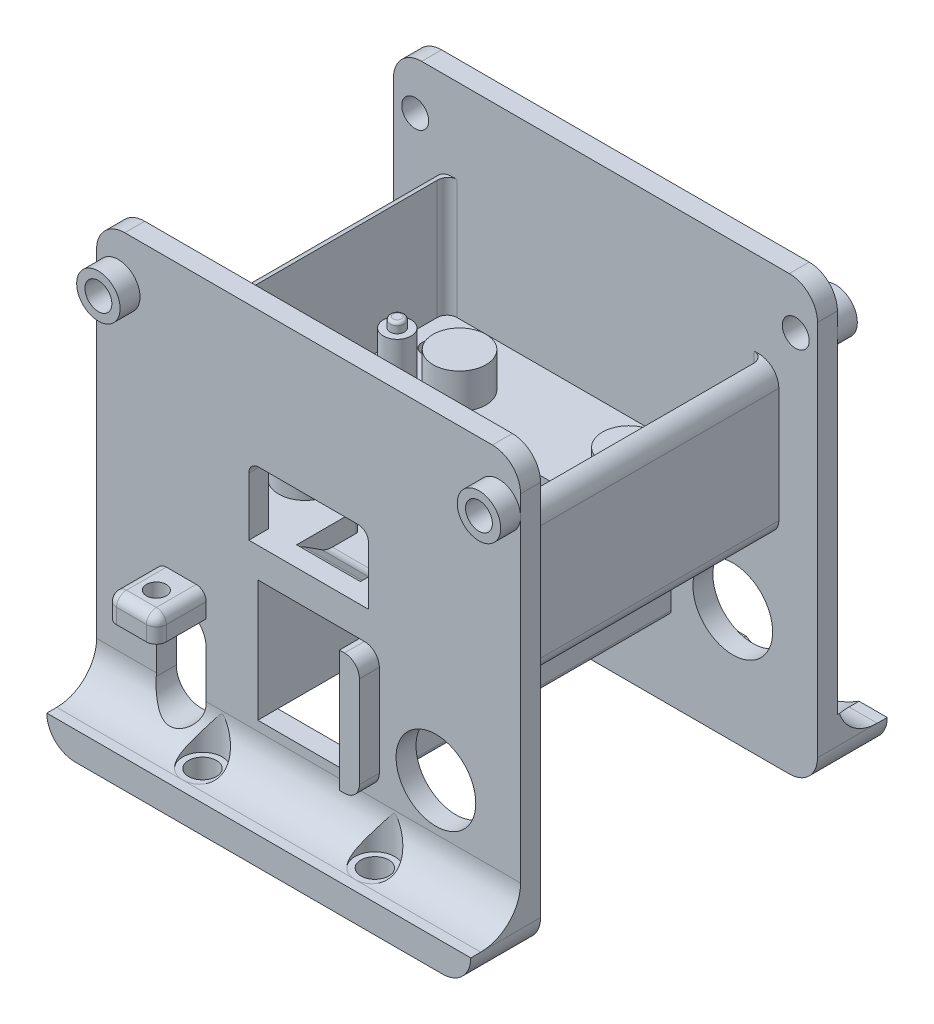
SolidWorks part; units mm, degrees
other "标注1"
sketch "草图55" plane through (-21.28, -20, 20.9) normal (0, 0, 1) x (1, 0, 0)
material "尼龙 101"
ref_plane "前视基准面" through (0, 0, 0) normal (0, 0, 1) x (1, 0, 0)
ref_plane "上视基准面" through (0, 0, 0) normal (0, 1, 0) x (1, 0, 0)
ref_plane "右视基准面" through (0, 0, 0) normal (1, 0, 0) x (0, 0, -1)
other "Configuration Table"
sketch "草图1" plane through (0, 0, 0) normal (0, 1, 0) x (1, 0, 0)
  line L1 (-15.9, 13.9) -> (15.9, 13.9)
  line L2 (-15.9, 13.9) -> (-15.9, -13.9)
  line L3 (-15.9, -13.9) -> (15.9, -13.9)
  line L4 (15.9, 13.9) -> (15.9, -13.9)
  line L5 (-15.9, 13.9) -> (15.9, -13.9) construction
  line L6 (-15.9, -13.9) -> (15.9, 13.9) construction
  point P0 (0, 0)
  dimension "D1" = 31.8
  dimension "D2" = 27.8
extrude "凸台-拉伸1" add sketch "草图1" along normal blind 3
sketch "草图2" plane through (0, 3, 0) normal (0, 1, 0) x (1, 0, 0)
  line L0 (0, 0) -> (0, 5.35) construction
  line L1 (-5.35, 5.35) -> (5.35, 5.35)
  line L2 (5.35, 5.35) -> (5.35, -7.55)
  line L3 (5.35, -7.55) -> (4.35, -7.55)
  line L4 (4.35, -7.55) -> (4.35, 4.35)
  line L5 (4.35, 4.35) -> (-4.35, 4.35)
  line L6 (-4.35, -7.55) -> (-4.35, 4.35)
  line L7 (-5.35, -7.55) -> (-4.35, -7.55)
  line L8 (-5.35, 5.35) -> (-5.35, -7.55)
  point P9 (0, 4.35)
  dimension "D1" = 8.7
  dimension "D2" = 11.9
  dimension "D3" = 4.35
  dimension "D4" = 1
  dimension "D5" = 1
extrude "凸台-拉伸2" add sketch "草图2" along normal blind 1.5
sketch "草图5" plane through (0, 3, 0) normal (0, 1, 0) x (1, 0, 0)
  line L0 (0, 13.9) -> (0, 0) construction
  line L1 (15.9, 13.9) -> (-15.9, 13.9) construction
  line L2 (0, 0) -> (15.9, 0) construction
  line L3 (15.9, -13.9) -> (15.9, 13.9) construction
  circle A0 centre (12.5, 5.5) radius 1.4
  circle A1 centre (12.5, -5.5) radius 1.4
  circle A2 centre (-12.5, -5.5) radius 1.4
  circle A3 centre (-12.5, 5.5) radius 1.4
  dimension "D1" = 2.8
  dimension "D2" = 25
  dimension "D3" = 11
extrude "凸台-拉伸3" add sketch "草图5" along normal blind 4.5
sketch "草图6" plane through (0, 7.5, 0) normal (0, 1, 0) x (1, 0, 0)
  circle A0 centre (-12.5, -5.5) radius 0.725
  circle A1 centre (-12.5, 5.5) radius 0.725
  circle A2 centre (12.5, 5.5) radius 0.725
  circle A3 centre (12.5, -5.5) radius 0.725
  dimension "D1" = 1.45
extrude "凸台-拉伸4" add sketch "草图6" along normal blind 1
sketch "草图7" plane through (0, 3, 0) normal (0, 1, 0) x (1, 0, 0)
  line L0 (0, 0) -> (0, 13.9) construction
  line L1 (15.9, 13.9) -> (-15.9, 13.9) construction
  line L2 (0, 0) -> (15.9, 0) construction
  line L3 (15.9, -13.9) -> (15.9, 13.9) construction
  circle A0 centre (13.5, 10) radius 1
  circle A1 centre (-13.5, 10) radius 1
  circle A2 centre (-13.5, -10) radius 1
  circle A3 centre (13.5, -10) radius 1
  dimension "D1" = 2
  dimension "D2" = 20
  dimension "D3" = 27
extrude "切除-拉伸1" cut sketch "草图7" against normal blind 10
sketch "草图8" plane through (0, 0, 0) normal (0, -1, 0) x (1, 0, 0)
  circle A0 centre (-13.5, 10) radius 2
  circle A1 centre (13.5, 10) radius 2
  circle A2 centre (13.5, -10) radius 2
  circle A3 centre (-13.5, -10) radius 2
  dimension "D1" = 4
extrude "切除-拉伸2" cut sketch "草图8" against normal blind 1
fillet "圆角1" radius 1 4 edges at (-15.9, 1.5, -13.9) (15.9, 1.5, -13.9) (-15.9, 1.5, 13.9) (15.9, 1.5, 13.9)
sketch "草图9" plane through (0, 3, 0) normal (0, 1, 0) x (1, 0, 0)
  line L0 (0, 13.9) -> (0, 0) construction
  line L1 (14.9, 13.9) -> (-14.9, 13.9) construction
  line L2 (0, 0) -> (15.9, 0) construction
  line L3 (15.9, -12.9) -> (15.9, 12.9) construction
  circle A0 centre (8.5, 7.75) radius 2.65
  circle A1 centre (-8.5, 7.75) radius 2.65
  circle A2 centre (-8.5, -7.75) radius 2.65
  circle A3 centre (8.5, -7.75) radius 2.65
  dimension "D1" = 17
  dimension "D2" = 15.5
  dimension "D3" = 5.3
extrude "凸台-拉伸5" add sketch "草图9" along normal blind 3.5
fillet "圆角2" radius 0.3 4 edges at (12.5, 8.5, -4.775) (12.5, 8.5, 6.225) (-12.5, 8.5, 6.225) (-12.5, 8.5, -4.775)
sketch "草图15" plane through (0, 3, 0) normal (0, 1, 0) x (1, 0, 0)
  line L0 (0, 0) -> (0, 13.9) construction
  line L1 (14.9, 13.9) -> (-14.9, 13.9) construction
  line L2 (-4.35, 4.35) -> (4.35, 4.35)
  line L3 (4.35, 4.35) -> (4.35, -7.55)
  line L4 (4.35, -7.55) -> (3.2, -7.55)
  line L5 (3.2, -7.55) -> (3.2, -13.9)
  line L6 (-14.9, -13.9) -> (14.9, -13.9) construction
  line L7 (3.2, -13.9) -> (-3.2, -13.9)
  line L8 (-3.2, -7.55) -> (-3.2, -13.9)
  line L9 (-4.35, -7.55) -> (-3.2, -7.55)
  line L10 (-4.35, 4.35) -> (-4.35, -7.55)
  line L11 (4.35, 4.35) -> (4.35, -7.55) construction
  point P14 (0, -13.9)
  point P17 (0, 4.35)
  dimension "D1" = 6.4
extrude "切除-拉伸8" cut sketch "草图15" against normal blind 2
sketch "草图17" plane through (0, 4.5, 0) normal (0, 1, 0) x (1, 0, 0)
  line L8 (-4.35, -7.55) -> (-4.35, 4.35)
  line L9 (-4.35, 4.35) -> (4.35, 4.35)
  line L10 (4.35, 4.35) -> (4.35, -7.55)
  line L11 (4.35, -7.55) -> (5.35, -7.55)
  line L12 (5.35, -7.55) -> (5.35, 5.35)
  line L13 (5.35, 5.35) -> (-5.35, 5.35)
  line L14 (-5.35, 5.35) -> (-5.35, -7.55)
  line L15 (-5.35, -7.55) -> (-4.35, -7.55)
  line L16 (-4.35, -7.55) -> (-4.35, 4.35)
  line L17 (-4.35, 4.35) -> (4.35, 4.35)
  line L18 (4.35, 4.35) -> (4.35, -7.55)
  line L19 (4.35, -7.55) -> (5.35, -7.55)
  line L20 (5.35, -7.55) -> (5.35, 5.35)
  line L21 (5.35, 5.35) -> (-5.35, 5.35)
  line L22 (-5.35, 5.35) -> (-5.35, -7.55)
  line L23 (-5.35, -7.55) -> (-4.35, -7.55)
  dimension "D1" = 0
extrude "切除-拉伸9" cut sketch "草图17" against normal blind 1.5
sketch "草图18" plane through (3.2, 0, 0) normal (-1, 0, 0) x (0, 0, 1)
  line L0 (13.9, 1) -> (10.9, 1)
  line L2 (13.9, 1) -> (13.9, 3) construction
  line L3 (13.9, 2.6) -> (13.9, 1)
  line L5 (13.9, 3) -> (13.9, 0) construction
  line L6 (13.9, 2.6) -> (13.4, 2.6)
  line L7 (13.4, 2.6) -> (10.9, 1)
  line L8 (13.9, 3) -> (12.9, 3) construction
  dimension "D1" = 3
  dimension "D2" = 0.4
  dimension "D3" = 0.5
extrude "凸台-拉伸6" add sketch "草图18" along normal up to surface (6.4 mm away) up to face at (-3.2, 2, 10.725)
fillet "圆角3" radius 2 1 edges at (0, 1, 10.9)
fillet "圆角5" radius 1 1 edges at (0, 2.6, 13.4)
fillet "圆角6" radius 0.4 2 edges at (3.2, 2, 7.55) (-3.2, 2, 7.55)
sketch "草图21" plane through (0, 0, 0) normal (0, -1, 0) x (1, 0, 0)
  line L0 (-14.9, 13.9) -> (14.9, 13.9) construction
  line L1 (-15.9, -12.9) -> (-15.9, 12.9) construction
  line L2 (14.9, -13.9) -> (-14.9, -13.9) construction
  line L3 (15.9, 12.9) -> (15.9, -12.9) construction
  line L4 (-14.9, 13.9) -> (14.9, 13.9)
  line L5 (-15.9, -12.9) -> (-15.9, 12.9)
  line L6 (14.9, -13.9) -> (-14.9, -13.9)
  line L7 (15.9, 12.9) -> (15.9, -12.9)
  line L9 (-17.4, 15.9) -> (17.4, 15.9)
  line L10 (-17.4, 15.9) -> (-17.4, -15.9)
  line L11 (-17.4, -15.9) -> (17.4, -15.9)
  line L12 (17.4, 15.9) -> (17.4, -15.9)
  arc A0 (15.9, 12.9) -> (14.9, 13.9) centre (14.9, 12.9) ccw construction
  arc A1 (-14.9, 13.9) -> (-15.9, 12.9) centre (-14.9, 12.9) ccw construction
  arc A2 (-15.9, -12.9) -> (-14.9, -13.9) centre (-14.9, -12.9) ccw construction
  arc A3 (14.9, -13.9) -> (15.9, -12.9) centre (14.9, -12.9) ccw construction
  arc A4 (15.9, 12.9) -> (14.9, 13.9) centre (14.9, 12.9) ccw
  arc A5 (-14.9, 13.9) -> (-15.9, 12.9) centre (-14.9, 12.9) ccw
  arc A6 (-15.9, -12.9) -> (-14.9, -13.9) centre (-14.9, -12.9) ccw
  arc A7 (14.9, -13.9) -> (15.9, -12.9) centre (14.9, -12.9) ccw
  dimension "D1" = 1.5
  dimension "D2" = 1.5
  dimension "D3" = 2
  dimension "D4" = 2
extrude "凸台-拉伸7" add sketch "草图21" against normal blind 15
sketch "草图22" plane through (0, 0, 15.9) normal (0, 0, 1) x (1, 0, 0)
  line L2 (-21.28, 0) -> (-21.28, 20.67)
  line L3 (-18.45, 23.5) -> (18.45, 23.5)
  line L4 (21.28, 0) -> (21.28, 20.67)
  line L5 (-21.28, 0) -> (21.28, 23.5) construction
  line L6 (-21.28, 23.5) -> (21.28, 0) construction
  line L7 (0, 0) -> (0, 23.5) construction
  line L10 (-21.28, 0) -> (-21.28, -17.17)
  line L11 (-18.45, -20) -> (18.45, -20)
  line L12 (21.28, 0) -> (21.28, -17.17)
  arc A0 (-21.28, 20.67) -> (-18.45, 23.5) centre (-18.45, 20.67) cw
  arc A1 (18.45, 23.5) -> (21.28, 20.67) centre (18.45, 20.67) cw
  arc A4 (18.45, -20) -> (21.28, -17.17) centre (18.45, -17.17) ccw
  arc A5 (-21.28, -17.17) -> (-18.45, -20) centre (-18.45, -17.17) ccw
  circle A9 centre (19.1, 18.67) radius 1.35
  circle A10 centre (-19.1, 18.67) radius 1.35
  point P4 (0, 11.75)
  point P22 (21.28, -20)
  dimension "D3" = 2.83
  dimension "D4" = 2.83
  dimension "D8" = 2.83
  dimension "D1" = 42.56
  dimension "D2" = 23.5
  dimension "D7" = 20
extrude "凸台-拉伸8" add sketch "草图22" against normal blind 2
sketch "草图24" plane through (0, 0, -15.9) normal (0, 0, -1) x (-1, 0, 0)
  line L5 (-18.45, -20) -> (18.45, -20)
  line L6 (-18.45, -20) -> (18.45, -20)
  line L21 (21.28, -17.17) -> (21.28, 20.67)
  line L22 (18.45, 23.5) -> (-18.45, 23.5)
  line L23 (-21.28, 20.67) -> (-21.28, -17.17)
  line L37 (21.28, -17.17) -> (21.28, 20.67)
  line L38 (18.45, 23.5) -> (-18.45, 23.5)
  line L39 (-21.28, 20.67) -> (-21.28, -17.17)
  arc A2 (21.28, 20.67) -> (18.45, 23.5) centre (18.45, 20.67) ccw
  arc A3 (-18.45, 23.5) -> (-21.28, 20.67) centre (-18.45, 20.67) ccw
  arc A4 (21.28, 20.67) -> (18.45, 23.5) centre (18.45, 20.67) ccw
  arc A5 (-18.45, 23.5) -> (-21.28, 20.67) centre (-18.45, 20.67) ccw
  circle A10 centre (19.1, 18.67) radius 1.35 construction
  circle A11 centre (-19.1, 18.67) radius 1.35 construction
  arc A12 (-21.28, -17.17) -> (-18.45, -20) centre (-18.45, -17.17) ccw
  arc A13 (-21.28, -17.17) -> (-18.45, -20) centre (-18.45, -17.17) ccw
  arc A14 (18.45, -20) -> (21.28, -17.17) centre (18.45, -17.17) ccw
  arc A15 (18.45, -20) -> (21.28, -17.17) centre (18.45, -17.17) ccw
  circle A16 centre (19.1, 18.67) radius 1.35
  circle A17 centre (-19.1, 18.67) radius 1.35
  dimension "D1" = 0
extrude "凸台-拉伸9" add sketch "草图24" against normal blind 2
sketch "草图25" plane through (0, 0, 15.9) normal (0, 0, 1) x (1, 0, 0)
  line L1 (-5, 9.85) -> (5, 9.85)
  line L2 (-6, 8.85) -> (-6, 3)
  line L4 (6, 8.85) -> (6, 3)
  line L5 (-6, 3) -> (6, 3)
  line L9 (-6, 3) -> (6, 9.85) construction
  arc A0 (5, 9.85) -> (6, 8.85) centre (5, 8.85) cw
  arc A1 (-5, 9.85) -> (-6, 8.85) centre (-5, 8.85) ccw
  point P5 (6, 9.85)
  point P8 (0, 6.425)
  point P9 (-6, 9.85)
  dimension "D2" = 1
  dimension "D1" = 12
extrude "切除-拉伸10" cut sketch "草图25" against normal blind 2
sketch "草图27" plane through (0, 0, 15.9) normal (0, 0, 1) x (1, 0, 0)
  line L0 (-5.1, 0) -> (5.1, -12.2) construction
  line L5 (-5.1, 0) -> (5.1, 0) construction
  line L16 (-17.4, 0) -> (17.4, 0) construction
  line L18 (-5.1, 0) -> (-5.1, -12.2)
  line L20 (5.1, 0) -> (5.1, -12.2)
  line L21 (-6.6, 0) -> (-6.6, -11.7)
  line L26 (6.6, 0) -> (6.6, -11.7)
  line L31 (-6.6, 0) -> (-5.1, 0)
  line L33 (-6.1, -12.2) -> (-5.1, -12.2)
  line L34 (-6.6, 1.5) -> (6.6, 1.5) construction
  line L35 (0, 0) -> (0, -4.0507) construction
  line L36 (6.6, 1.5) -> (6.6, -13.7) construction
  line L37 (-6.6, 1.5) -> (-6.6, -13.7) construction
  line L38 (5.1, 0) -> (6.6, 0)
  line L39 (-6.6, -13.7) -> (6.6, -13.7) construction
  line L40 (-5.1, -12.2) -> (5.1, -12.2) construction
  line L41 (5.1, -12.2) -> (6.1, -12.2)
  arc A4 (6.1, -12.2) -> (6.6, -11.7) centre (6.1, -11.7) ccw
  arc A5 (-6.6, -11.7) -> (-6.1, -12.2) centre (-6.1, -11.7) ccw
  point P6 (-2.5, 0)
  point P7 (6.9808, -17.5163)
  point P19 (6.6, -12.2)
  point P24 (0, -6.1)
  dimension "D4" = 0.5
  dimension "D1" = 10.2
  dimension "D2" = 12.2
  dimension "D3" = 1.5
extrude "凸台-拉伸10" add sketch "草图27" against normal up to surface (29.8 mm away) up to face at (0, 8.25, -13.9)
sketch "草图35" plane through (0, 0, 15.9) normal (0, 0, 1) x (1, 0, 0)
  line L1 (-5.1, 0) -> (5.1, 0)
  line L2 (-5.1, 0) -> (-5.1, -12.2)
  line L3 (-5.1, -12.2) -> (5.1, -12.2)
  line L4 (5.1, 0) -> (5.1, -12.2)
extrude "切除-拉伸14" cut sketch "草图35" against normal through all
sketch "草图43" plane through (0, 0, 15.9) normal (0, 0, 1) x (1, 0, 0)
  line L0 (-21.28, -17.17) -> (21.28, -17.17)
  line L1 (-18.45, -20) -> (18.45, -20) construction
  line L2 (-18.45, -20) -> (18.45, -20)
  arc A1 (18.45, -20) -> (21.28, -17.17) centre (18.45, -17.17) ccw construction
  arc A3 (-21.28, -17.17) -> (-18.45, -20) centre (-18.45, -17.17) ccw construction
  arc A4 (18.45, -20) -> (21.28, -17.17) centre (18.45, -17.17) ccw
  arc A5 (-21.28, -17.17) -> (-18.45, -20) centre (-18.45, -17.17) ccw
extrude "凸台-拉伸14" add sketch "草图43" along normal blind 5
sketch "草图44" plane through (-21.28, 0, 0) normal (-1, 0, 0) x (0, 0, 1)
  line L3 (15.9, -13.17) -> (15.9, -17.17)
  line L4 (15.9, -17.17) -> (19.9, -17.17)
  arc A0 (19.9, -17.17) -> (15.9, -13.17) centre (19.9, -13.17) cw
  point P8 (15.9, -17.17)
  dimension "D1" = 4
extrude "凸台-拉伸15" add sketch "草图44" against normal up to surface (42.56 mm away) up to face at (21.28, 1.75, 14.9)
sketch "草图45" plane through (0, 0, -15.9) normal (0, 0, -1) x (-1, 0, 0)
  line L0 (-18.45, -20) -> (18.45, -20) construction
  line L1 (-21.28, -17.17) -> (21.28, -17.17) construction
  line L2 (-18.45, -20) -> (18.45, -20)
  line L3 (-21.28, -17.17) -> (21.28, -17.17)
  arc A0 (-21.28, -17.17) -> (-18.45, -20) centre (-18.45, -17.17) ccw construction
  arc A1 (18.45, -20) -> (21.28, -17.17) centre (18.45, -17.17) ccw construction
  arc A2 (-21.28, -17.17) -> (-18.45, -20) centre (-18.45, -17.17) ccw
  arc A3 (18.45, -20) -> (21.28, -17.17) centre (18.45, -17.17) ccw
extrude "凸台-拉伸16" add sketch "草图45" along normal blind 5
sketch "草图46" plane through (21.28, 0, 0) normal (1, 0, 0) x (0, 0, -1)
  line L0 (15.9, -13.17) -> (15.9, -17.17)
  line L1 (15.9, -17.17) -> (19.9, -17.17)
  arc A0 (15.9, -13.17) -> (19.9, -17.17) centre (19.9, -13.17) ccw
  point P7 (15.9, -17.17)
  dimension "D1" = 4
extrude "凸台-拉伸17" add sketch "草图46" against normal up to surface (42.56 mm away) up to face at (-21.28, 1.75, -14.9)
sketch "草图36" plane through (0, 0, 15.9) normal (0, 0, 1) x (1, 0, 0)
  line L0 (-5.1, 0) -> (5.1, -12.2) construction
  line L1 (5.1, 0) -> (-5.1, -12.2) construction
  line L2 (-5.1, -12.2) -> (5.1, -12.2) construction
  line L3 (-5.1, 0) -> (-5.1, -12.2) construction
  line L6 (-5.1, -12.2) -> (-5.1, -13.2) construction
  line L7 (-5.1, -13.2) -> (22.8364, -13.2) construction
  line L8 (21.28, -13.17) -> (21.28, 20.67) construction
  line L10 (-15.28, -8.4815) -> (-15.28, -13.4815)
  line L12 (-10.28, -13.4815) -> (-10.28, -8.4815)
  circle A0 centre (0, -6.1) radius 4.5 construction
  circle A3 centre (12.78, -8.4815) radius 8.5 construction
  circle A6 centre (12.78, -8.4815) radius 5.75 construction
  circle A7 centre (12.78, -8.4815) radius 4
  arc A9 (-10.28, -8.4815) -> (-15.28, -8.4815) centre (-12.78, -8.4815) ccw
  arc A11 (-15.28, -13.4815) -> (-10.28, -13.4815) centre (-12.78, -13.4815) ccw
  point P11 (0, -6.1)
  dimension "D1" = 9
  dimension "D2" = 17
  dimension "D3" = 8
  dimension "D4" = 9
  dimension "D5" = 11.5
extrude "切除-拉伸15" cut sketch "草图36" against normal through all both and the other way through all
sketch "草图37" plane through (0, 0, 15.9) normal (0, 0, 1) x (1, 0, 0)
  line L0 (-15.28, -5.9815) -> (-15.28, -3.4815)
  line L1 (-15.28, -3.4815) -> (-10.28, -3.4815)
  line L2 (-10.28, -3.4815) -> (-10.28, -5.9815)
  line L3 (-15.28, -5.9815) -> (-10.28, -5.9815)
extrude "凸台-拉伸11" add sketch "草图37" along normal blind 5
sketch "草图38" plane through (0, 0, -15.9) normal (0, 0, -1) x (-1, 0, 0)
  line L0 (15.28, -3.4815) -> (15.28, -5.9815) construction
  line L1 (10.28, -5.9815) -> (10.28, -3.4815) construction
  line L2 (10.28, -3.4815) -> (15.28, -3.4815) construction
  line L3 (15.28, -3.4815) -> (15.28, -5.9815)
  line L4 (10.28, -5.9815) -> (10.28, -3.4815)
  line L5 (10.28, -3.4815) -> (15.28, -3.4815)
  line L6 (10.28, -5.9815) -> (15.28, -5.9815)
extrude "凸台-拉伸12" add sketch "草图38" along normal blind 5
fillet "圆角7" radius 1 2 edges at (-10.28, -4.7315, 20.9) (-15.28, -4.7315, 20.9)
fillet "圆角8" radius 1 2 edges at (-10.28, -4.7315, -20.9) (-15.28, -4.7315, -20.9)
sketch "草图41" plane through (0, 0, 15.9) normal (0, 0, 1) x (1, 0, 0)
  line L1 (5.1, 0) -> (5.6, 0)
  line L2 (5.1, 0) -> (5.1, -12.2)
  line L3 (5.1, -12.2) -> (5.6, -12.2)
  line L4 (7.1, -1.5) -> (7.1, -10.7)
  arc A0 (5.6, -12.2) -> (7.1, -10.7) centre (5.6, -10.7) ccw
  arc A1 (7.1, -1.5) -> (5.6, 0) centre (5.6, -1.5) ccw
  dimension "D1" = 1.5
  dimension "D2" = 2
extrude "凸台-拉伸13" add sketch "草图41" along normal blind 2
sketch "草图42" plane through (0, -3.4815, 0) normal (0, 1, 0) x (1, 0, 0)
  line L0 (-14.9871, 20.6071) -> (-10.28, 15.9) construction
  line L1 (-15.28, -15.9) -> (-10.5729, -20.6071) construction
  line L2 (-10.5729, 20.6071) -> (-15.28, 15.9) construction
  line L3 (-10.28, -15.9) -> (-14.9871, -20.6071) construction
  arc A0 (-14.28, 20.9) -> (-15.28, 19.9) centre (-14.28, 19.9) ccw construction
  arc A1 (-10.28, 19.9) -> (-11.28, 20.9) centre (-11.28, 19.9) ccw construction
  arc A2 (-11.28, -20.9) -> (-10.28, -19.9) centre (-11.28, -19.9) ccw construction
  arc A3 (-15.28, -19.9) -> (-14.28, -20.9) centre (-14.28, -19.9) ccw construction
  circle A4 centre (-12.78, -18.4) radius 1
  circle A5 centre (-12.78, 18.4) radius 1
  point P24 (-12.78, 18.4)
  point P25 (-12.78, -18.4)
  dimension "D1" = 2
  dimension "D2" = 2
sketch "草图49" plane through (0, -20, 0) normal (0, -1, 0) x (1, 0, 0)
  line L5 (8.65, 17.9) -> (-8.65, -17.9) construction
  line L6 (-8.65, 17.9) -> (8.65, 17.9) construction
  line L7 (-8.65, 17.9) -> (-8.65, -17.9) construction
  line L8 (-8.65, -17.9) -> (8.65, -17.9) construction
  line L9 (8.65, 17.9) -> (8.65, -17.9) construction
  circle A1 centre (-8.65, 17.9) radius 1.4
  circle A2 centre (8.65, 17.9) radius 1.4
  circle A3 centre (8.65, -17.9) radius 1.4
  circle A4 centre (-8.65, -17.9) radius 1.4
  point P6 (0, 0)
  dimension "D1" = 17.3
  dimension "D2" = 35.8
extrude "切除-拉伸17" cut sketch "草图49" against normal blind 6
sketch "草图51" plane through (0, 0, -15.9) normal (0, 0, -1) x (-1, 0, 0)
  circle A3 centre (-12.78, -8.4815) radius 10.3764
extrude "切除-拉伸18" cut sketch "草图51" along normal blind 6
sketch "草图52" plane through (0, -17.17, 0) normal (0, 1, 0) x (1, 0, 0)
  circle A3 centre (-8.65, -17.9) radius 1.99
  circle A4 centre (-8.65, 17.9) radius 1.99
  circle A6 centre (8.65, -17.9) radius 1.99
extrude "切除-拉伸20" cut sketch "草图52" along normal blind 4
fillet "圆角10" radius 1 5 edges at (-14.9871, -3.4815, 20.6071) (-12.78, -3.4815, 20.9) (-10.5729, -3.4815, 20.6071) (-10.28, -3.4815, 17.9) (-15.28, -3.4815, 17.9)
fillet "圆角12" radius 1 5 edges at (-15.28, -3.4815, -17.9) (-14.9871, -3.4815, -20.6071) (-12.78, -3.4815, -20.9) (-10.5729, -3.4815, -20.6071) (-10.28, -3.4815, -17.9)
extrude "切除-拉伸21" cut sketch "草图42" against normal blind 4
ref_plane "基准面7" through (0, 0, -6.3) normal (0, 0, -1) x (-1, 0, 0)
sketch "草图54" plane through (0, 0, -6.3) normal (0, 0, -1) x (-1, 0, 0)
  line L0 (-5.1, 0) -> (5.1, -12.2) construction
  line L1 (-5.1, 0) -> (5.1, 0)
  line L2 (-5.1, 0) -> (-5.1, -12.2)
  line L3 (-5.1, -12.2) -> (5.1, -12.2)
  line L4 (5.1, 0) -> (5.1, -12.2)
  line L5 (0, -1.6) -> (0, -10.6) construction
  circle A0 centre (0, -1.6) radius 0.8
  circle A1 centre (0, -10.6) radius 0.8
  circle A2 centre (0, -6.1) radius 1.8
  point P8 (0, -6.1)
  point P11 (0, -6.1)
  dimension "D1" = 9
  dimension "D2" = 0
  dimension "D3" = 0
extrude "凸台-拉伸18" add sketch "草图54" along normal blind 2
fillet "圆角13" radius 1.5 2 edges at (17.4, 0, 0) (-17.4, 0, 0)
sketch "草图56" plane through (0, 0, -15.9) normal (0, 0, -1) x (-1, 0, 0)
  circle A1 centre (19.1, 18.67) radius 1.35 construction
  circle A2 centre (19.1, 18.67) radius 1.35
  circle A3 centre (19.1, 18.67) radius 2.1725
  circle A4 centre (-19.1, 18.67) radius 1.35
  circle A5 centre (-19.1, 18.67) radius 2.18
extrude "凸台-拉伸19" add sketch "草图56" along normal blind 2
sketch "草图57" plane through (0, 0, 15.9) normal (0, 0, 1) x (1, 0, 0)
  circle A0 centre (-19.1, 18.67) radius 1.35
  circle A1 centre (-19.1, 18.67) radius 2.18
  circle A2 centre (19.1, 18.67) radius 1.3466
  circle A3 centre (19.1, 18.67) radius 2.18
extrude "凸台-拉伸20" add sketch "草图57" along normal blind 2
fillet "圆角14" radius 2 2 edges at (-17.4, 15, 0) (17.4, 15, 0)
